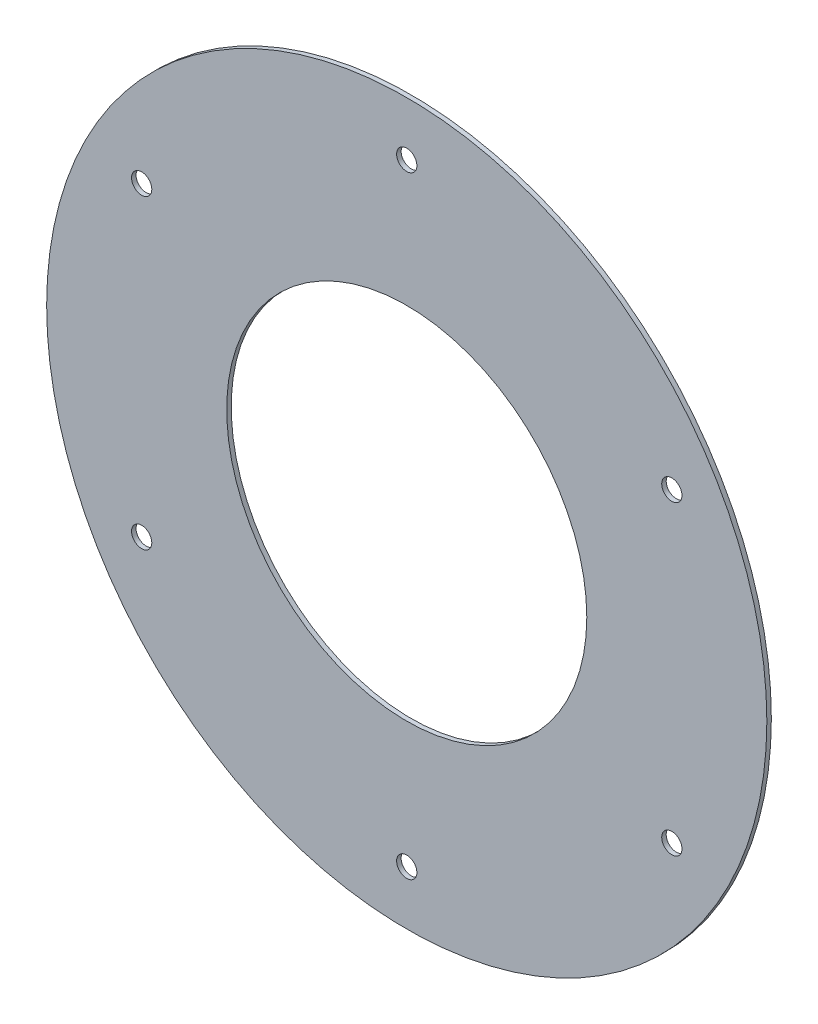
SolidWorks part; units mm, degrees
ref_plane "Front Plane" through (0, 0, 0) normal (0, 0, 1) x (1, 0, 0)
ref_plane "Top Plane" through (0, 0, 0) normal (0, 1, 0) x (1, 0, 0)
ref_plane "Right Plane" through (0, 0, 0) normal (1, 0, 0) x (0, 0, -1)
sketch "Sketch1" plane through (0, 0, 0) normal (0, 0, 1) x (1, 0, 0)
  circle A0 centre (0, 0) radius 127
  dimension "D1" = 254
extrude "Boss-Extrude1" add sketch "Sketch1" along normal blind 1.5875
sketch "Sketch2" plane through (0, 0, 1.5875) normal (0, 0, 1) x (1, 0, 0)
  circle A0 centre (0, 0) radius 107.95
  point P1 (0, 107.95)
  point P6 (93.4874, 53.975)
  point P9 (93.4874, -53.975)
  point P10 (0, -107.95)
  point P11 (-93.4874, -53.975)
  point P12 (-93.4874, 53.975)
  dimension "D1" = 215.9
  dimension "D2" = 6
hole_wizard "1/4 Clearance Hole1" positions "Sketch2" profile "Sketch3" hole size "1/4" standard "ANSI Inch" end condition up to next
sketch "Sketch3" plane through (-93.4874, 53.975, 1.5875) normal (1, 0, 0) x (0, -1, 0)
  line L0 (0, 0) -> (0, 1.5875)
  line L1 (0, 1.5875) -> (3.5712, 1.5875)
  line L2 (3.5712, 1.5875) -> (3.5712, 0)
  line L5 (3.5712, 0) -> (0, 0)
  line L11 (0, -6.35) -> (0, 107.95) construction
  dimension "Thru Hole Dia." = 7.1425
  dimension "Thru Hole Depth" = 1.5875
sketch "Sketch4" plane through (0, 0, 1.5875) normal (0, 0, 1) x (1, 0, 0)
  circle A0 centre (0, 0) radius 63.5
  dimension "D1" = 127
extrude "Cut-Extrude1" cut sketch "Sketch4" against normal up to next
